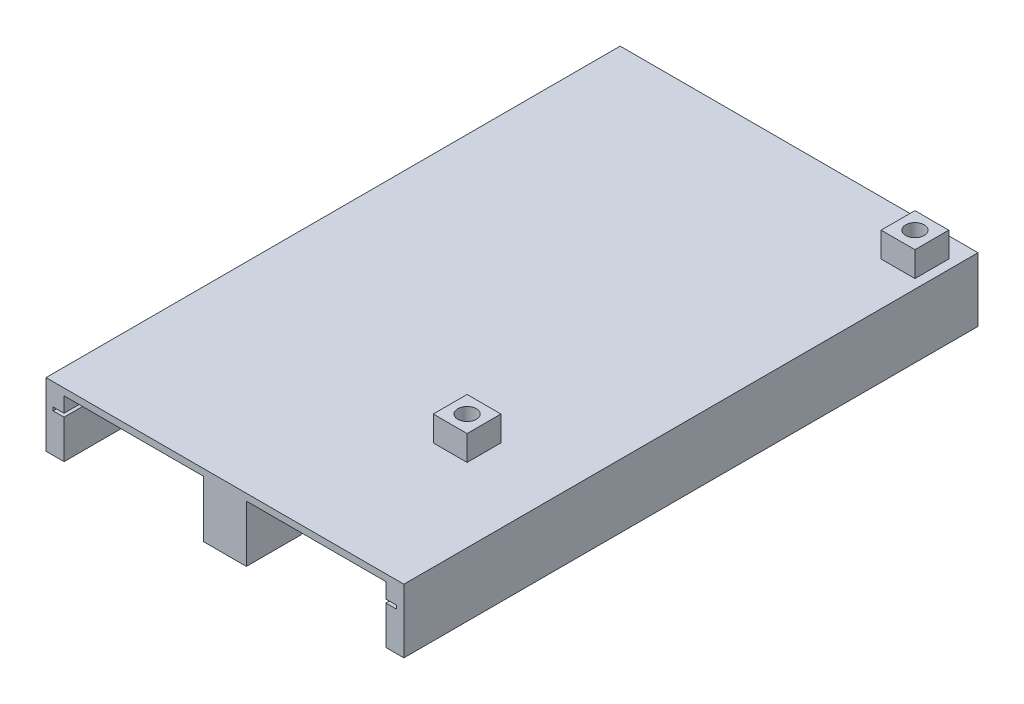
SolidWorks part; units mm, degrees
material "PLA"
ref_plane "Спереди" through (0, 0, 0) normal (0, 0, 1) x (1, 0, 0)
ref_plane "Сверху" through (0, 0, 0) normal (0, 1, 0) x (1, 0, 0)
ref_plane "Справа" through (0, 0, 0) normal (1, 0, 0) x (0, 0, -1)
sketch "Эскиз1" plane through (0, 0, 0) normal (0, 1, 0) x (1, 0, 0)
  line L0 (0, 0) -> (-4740.9496, 0) construction
  line L1 (0, 0) -> (0, -4740.9496) construction
  line L2 (35.675, 63.65) -> (39.675, 63.65)
  line L3 (-35.675, -63.65) -> (-39.675, -63.65)
  line L4 (-35.675, -63.65) -> (-35.675, 63.65)
  line L5 (-35.675, 63.65) -> (-39.675, 63.65)
  line L6 (-39.675, -63.65) -> (-39.675, 63.65)
  line L7 (-35.675, -63.65) -> (-39.675, 63.65) construction
  line L8 (-35.675, 63.65) -> (-39.675, -63.65) construction
  line L9 (39.675, -63.65) -> (39.675, 63.65)
  line L10 (35.675, -63.65) -> (39.675, -63.65)
  line L11 (35.675, -63.65) -> (35.675, 63.65)
  line L12 (35.675, 63.65) -> (39.675, -63.65) construction
  line L13 (35.675, -63.65) -> (39.675, 63.65) construction
  point P5 (-37.675, 0)
  point P14 (37.675, 0)
  dimension "D1" = 4
  dimension "D2" = 127.3
  dimension "D3" = 71.35
extrude "Бобышка-Вытянуть1" add sketch "Эскиз1" along normal blind 12.65
sketch "Эскиз2" plane through (0, 12.65, 0) normal (0, 1, 0) x (1, 0, 0)
  line L1 (39.675, 63.65) -> (-39.675, 63.65)
  line L2 (39.675, 63.65) -> (39.675, -63.65)
  line L3 (39.675, -63.65) -> (-39.675, -63.65)
  line L4 (-39.675, 63.65) -> (-39.675, -63.65)
extrude "Бобышка-Вытянуть2" add sketch "Эскиз2" along normal blind 1.5
sketch "Эскиз3" plane through (0, 0, -63.65) normal (0, 0, -1) x (-1, 0, 0)
  line L0 (0, 0) -> (0, 50000) construction
  line L1 (-35.675, 12.65) -> (-35.675, 0) construction
  line L2 (-35.675, 9.3) -> (-38.075, 9.3)
  line L3 (-35.675, 9.3) -> (-35.675, 8.55)
  line L4 (-35.675, 8.55) -> (-38.075, 8.55)
  line L5 (-38.075, 9.3) -> (-38.075, 8.55)
  line L6 (35.675, 8.55) -> (38.075, 8.55)
  line L7 (38.075, 9.3) -> (38.075, 8.55)
  line L8 (35.675, 9.3) -> (38.075, 9.3)
  line L9 (35.675, 9.3) -> (35.675, 8.55)
  line L10 (-39.675, 0) -> (-35.675, 0) construction
  dimension "D1" = 2.4
  dimension "D2" = 0.75
  dimension "D3" = 8.55
extrude "Вырез-Вытянуть1" cut sketch "Эскиз3" against normal through all from offset 1.5 offset against normal yes
sketch "Эскиз4" plane through (0, 12.65, 0) normal (0, -1, 0) x (1, 0, 0)
  line L0 (35.675, -63.65) -> (35.675, 63.65) construction
  line L1 (-35.675, -63.65) -> (35.675, -63.65)
  line L2 (-35.675, -63.65) -> (-35.675, -62.15)
  line L3 (-35.675, -62.15) -> (35.675, -62.15)
  line L4 (35.675, -63.65) -> (35.675, -62.15)
  dimension "D1" = 1.5
extrude "Бобышка-Вытянуть3" add sketch "Эскиз4" along normal up to surface (12.65 mm away) up to face at (37.675, 0, 0)
sketch "Эскиз6" plane through (0, 12.65, 0) normal (0, -1, 0) x (1, 0, 0)
  line L0 (35.675, -62.15) -> (35.675, 63.65) construction
  line L1 (32.325, -52.35) -> (24.825, -52.35)
  line L2 (32.325, -52.35) -> (32.325, -62.15)
  line L3 (32.325, -59.85) -> (24.825, -59.85) construction
  line L4 (24.825, -52.35) -> (24.825, -62.15)
  line L5 (32.325, -52.35) -> (24.825, -59.85) construction
  line L6 (32.325, -59.85) -> (24.825, -52.35) construction
  line L7 (35.675, -62.15) -> (-35.675, -62.15) construction
  line L8 (32.325, -62.15) -> (24.825, -62.15)
  circle A0 centre (28.575, -56.1) radius 2.1 construction
  point P0 (28.575, -56.1)
  dimension "D3" = 4.2
  dimension "D4" = 1.65
  dimension "D5" = 1.65
  dimension "D1" = 7.1
  dimension "D2" = 6.05
extrude "Бобышка-Вытянуть5" add sketch "Эскиз6" along normal blind 9.6
sketch "Эскиз7" plane through (0, 3.05, 0) normal (0, -1, 0) x (1, 0, 0)
  line L0 (24.825, -52.35) -> (32.325, -59.85) construction
  line L1 (32.325, -52.35) -> (24.825, -59.85) construction
  line L2 (32.325, -62.15) -> (32.325, -52.35) construction
  line L3 (24.825, -52.35) -> (24.825, -62.15) construction
  circle A0 centre (28.575, -56.1) radius 2.05
  dimension "D1" = 4.1
extrude "Вырез-Вытянуть2" cut sketch "Эскиз7" against normal blind 4.5
sketch "Эскиз8" plane through (0, 0, 0) normal (0, -1, 0) x (1, 0, 0)
  line L0 (-35.675, 63.65) -> (-35.675, -62.15) construction
  line L1 (-35.675, 38.05) -> (-38.075, 38.05)
  line L2 (-35.675, 38.05) -> (-35.675, 32.2)
  line L3 (-35.675, 32.2) -> (-38.075, 32.2)
  line L4 (-38.075, 38.05) -> (-38.075, 32.2)
  line L5 (0, 0) -> (0, 50000) construction
  line L6 (-35.675, -16.55) -> (-38.075, -16.55)
  line L7 (-35.675, -16.55) -> (-35.675, -22.4)
  line L8 (-35.675, -22.4) -> (-38.075, -22.4)
  line L9 (-38.075, -16.55) -> (-38.075, -22.4)
  line L10 (-39.675, 63.65) -> (-35.675, 63.65) construction
  line L11 (35.675, -22.4) -> (38.075, -22.4)
  line L12 (38.075, -16.55) -> (38.075, -22.4)
  line L13 (35.675, -16.55) -> (38.075, -16.55)
  line L14 (35.675, -16.55) -> (35.675, -22.4)
  line L15 (35.675, 32.2) -> (38.075, 32.2)
  line L16 (38.075, 38.05) -> (38.075, 32.2)
  line L17 (35.675, 38.05) -> (38.075, 38.05)
  line L18 (35.675, 38.05) -> (35.675, 32.2)
  line L19 (39.675, -63.65) -> (-39.675, -63.65) construction
  point P26 (0, -63.65)
  dimension "D1" = 2.4
  dimension "D2" = 5.85
  dimension "D3" = 48.75
  dimension "D4" = 25.6
extrude "Вырез-Вытянуть3" cut sketch "Эскиз8" against normal up to surface (8.55 mm away) up to face at (-36.875, 8.55, 0.75)
sketch "Эскиз10" plane through (0, 12.65, 0) normal (0, -1, 0) x (1, 0, 0)
  line L0 (-35.675, 63.65) -> (-35.675, -62.15) construction
  line L1 (-25.275, -51.75) -> (-28.275, -51.75)
  line L2 (-25.275, -51.75) -> (-25.275, -57.7)
  line L3 (-25.275, -57.7) -> (-28.275, -57.7)
  line L4 (-28.275, -51.75) -> (-28.275, -57.7)
  line L5 (24.825, -62.15) -> (-35.675, -62.15) construction
  line L6 (35.675, -62.15) -> (-35.675, -62.15) construction
  line L8 (15.225, -51.75) -> (18.225, -51.75)
  line L9 (15.225, -51.75) -> (15.225, -57.7)
  line L10 (15.225, -57.7) -> (18.225, -57.7)
  line L11 (18.225, -51.75) -> (18.225, -57.7)
  dimension "D1" = 10.4
  dimension "D2" = 4.45
  dimension "D3" = 10.4
  dimension "D4" = 3
  dimension "D5" = 50.9
extrude "Бобышка-Вытянуть6" add sketch "Эскиз10" along normal blind 3.95
sketch "Эскиз11" plane through (0, 12.65, 0) normal (0, -1, 0) x (1, 0, 0)
  line L1 (-25.275, -57.7) -> (15.225, -57.7)
  line L2 (-25.275, -57.7) -> (-25.275, -51.75)
  line L3 (-25.275, -51.75) -> (15.225, -51.75)
  line L4 (15.225, -57.7) -> (15.225, -51.75)
extrude "Бобышка-Вытянуть7" add sketch "Эскиз11" along normal blind 0.35
fillet "Скругление4" radius 4 1 edges at (-5.025, 12.65, -57.7)
fillet "Скругление5" radius 2 2 edges at (-26.775, 8.7, -57.7) (16.725, 8.7, -57.7)
sketch "Эскиз12" plane through (0, 0, -62.15) normal (0, 0, 1) x (1, 0, 0)
  line L0 (24.825, 12.65) -> (-35.675, 12.65) construction
  line L1 (15.475, 8) -> (-25.525, 8)
  line L2 (15.475, 8) -> (15.475, 12.65)
  line L12 (15.475, 12.65) -> (-25.525, 12.65)
  line L13 (-25.525, 8) -> (-25.525, 12.65)
  line L15 (-5.025, 12.3) -> (-5.025, 12.65) construction
  line L17 (-25.275, 12.3) -> (15.225, 12.3) construction
  point P13 (-5.025, 12.3)
  dimension "D1" = 4.65
  dimension "D2" = 41
extrude "Вырез-Вытянуть4" cut sketch "Эскиз12" against normal through all
sketch "Эскиз13" plane through (0, 12.65, 0) normal (0, -1, 0) x (1, 0, 0)
  line L0 (0, 63.65) -> (0, 50063.65) construction
  line L1 (-35.675, 63.65) -> (35.675, 63.65) construction
  line L2 (-4.75, 60.9) -> (-4.75, 63.65)
  line L3 (4.75, 60.9) -> (-4.75, 60.9) construction
  line L4 (4.75, 60.9) -> (4.75, 51.4)
  line L5 (4.75, 51.4) -> (-4.75, 51.4)
  line L6 (-4.75, 60.9) -> (-4.75, 51.4)
  line L7 (4.75, 60.9) -> (-4.75, 51.4) construction
  line L8 (4.75, 51.4) -> (-4.75, 60.9) construction
  line L9 (-4.75, 63.65) -> (4.75, 63.65)
  line L10 (4.75, 63.65) -> (4.75, 60.9)
  circle A0 centre (0, 56.15) radius 2.75 construction
  point P4 (0, 63.65)
  point P5 (0, 56.15)
  dimension "D1" = 5.5
  dimension "D2" = 9.5
  dimension "D3" = 7.5
extrude "Бобышка-Вытянуть8" add sketch "Эскиз13" along normal blind 12.55
sketch "Эскиз14" plane through (0, 0.1, 0) normal (0, -1, 0) x (1, 0, 0)
  line L0 (-4.75, 60.9) -> (4.75, 51.4) construction
  line L1 (4.75, 60.9) -> (-4.75, 51.4) construction
  line L2 (4.75, 51.4) -> (4.75, 63.65) construction
  line L3 (-4.75, 63.65) -> (-4.75, 51.4) construction
  line L4 (-4.75, 60.9) -> (4.75, 60.9) construction
  circle A0 centre (0, 56.15) radius 2.05
  dimension "D1" = 4.1
extrude "Вырез-Вытянуть5" cut sketch "Эскиз14" against normal blind 7
sketch "Эскиз15" plane through (0, 14.15, 0) normal (0, 1, 0) x (1, 0, 0)
  line L0 (39.675, -63.65) -> (39.675, 63.65) construction
  line L1 (30.1454, 59.1971) -> (37.6454, 59.1971)
  line L2 (30.1454, 59.1971) -> (30.1454, 51.6971)
  line L3 (30.1454, 51.6971) -> (37.6454, 51.6971)
  line L4 (37.6454, 59.1971) -> (37.6454, 51.6971)
  line L5 (30.1454, 59.1971) -> (37.6454, 51.6971) construction
  line L6 (30.1454, 51.6971) -> (37.6454, 59.1971) construction
  line L7 (15.8005, -25.7612) -> (23.3005, -25.7612)
  line L8 (15.8005, -25.7612) -> (15.8005, -33.2612)
  line L9 (15.8005, -33.2612) -> (23.3005, -33.2612)
  line L10 (23.3005, -25.7612) -> (23.3005, -33.2612)
  line L11 (15.8005, -25.7612) -> (23.3005, -33.2612) construction
  line L12 (15.8005, -33.2612) -> (23.3005, -25.7612) construction
  line L13 (-39.675, -63.65) -> (39.675, -63.65) construction
  point P0 (33.8954, 55.4471)
  point P5 (19.5505, -29.5112)
  dimension "D1" = 7.5
  dimension "D2" = 20.1245
  dimension "D3" = 34.1388
  dimension "D4" = 5.7796
  dimension "D5" = 119.0971
extrude "Бобышка-Вытянуть9" add sketch "Эскиз15" along normal blind 5.55
sketch "Эскиз16" plane through (0, 19.7, 0) normal (0, 1, 0) x (1, 0, 0)
  line L0 (30.1454, 59.1971) -> (37.6454, 51.6971) construction
  line L1 (37.6454, 59.1971) -> (30.1454, 51.6971) construction
  line L2 (23.3005, -25.7612) -> (15.8005, -33.2612) construction
  line L3 (15.8005, -25.7612) -> (23.3005, -33.2612) construction
  circle A0 centre (19.5505, -29.5112) radius 2.05
  circle A1 centre (33.8954, 55.4471) radius 2.05
  dimension "D1" = 4.1
extrude "Вырез-Вытянуть6" cut sketch "Эскиз16" against normal blind 5
